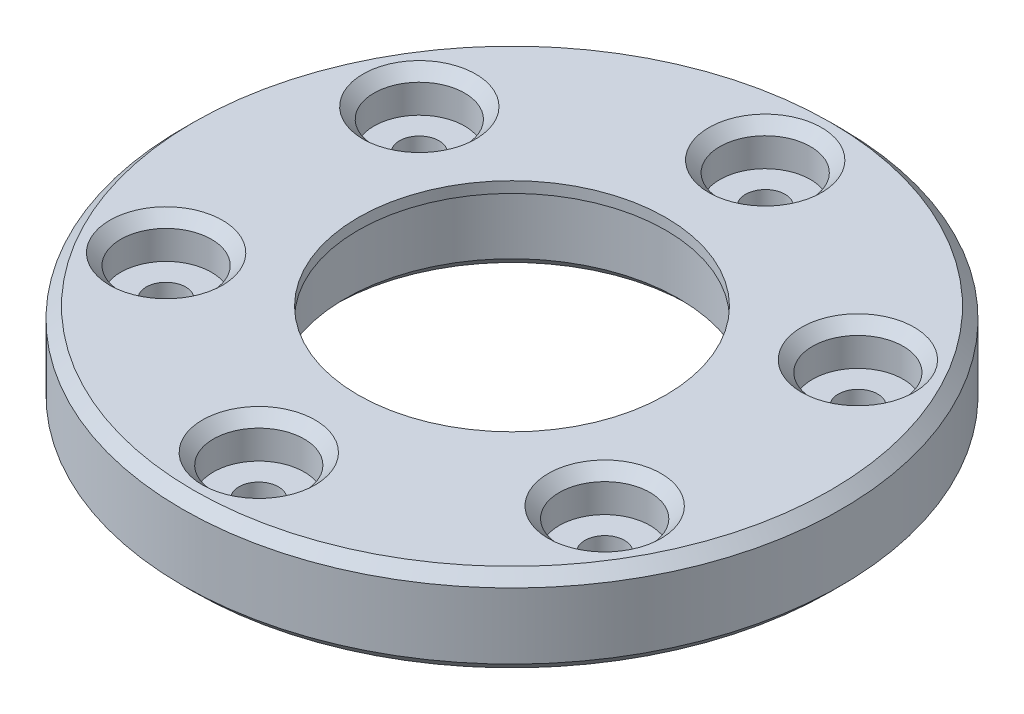
SolidWorks part; units mm, degrees
ref_plane "前视基准面" through (0, 0, 0) normal (0, 0, 1) x (1, 0, 0)
ref_plane "上视基准面" through (0, 0, 0) normal (0, 1, 0) x (1, 0, 0)
ref_plane "右视基准面" through (0, 0, 0) normal (1, 0, 0) x (0, 0, -1)
other "Configuration Table"
sketch "草图1" plane through (0, 0, 0) normal (0, 1, 0) x (1, 0, 0)
  circle A0 centre (0, 0) radius 7
  circle A1 centre (0, 0) radius 15
  circle A2 centre (0, 0) radius 11.525 construction
  circle A3 centre (0, 11.525) radius 2.065
  circle A4 centre (9.9809, 5.7625) radius 2.065
  circle A5 centre (9.9809, -5.7625) radius 2.065
  circle A6 centre (0, -11.525) radius 2.065
  circle A7 centre (-9.9809, -5.7625) radius 2.065
  circle A8 centre (-9.9809, 5.7625) radius 2.065
  point P19 (0, 0)
  dimension "D1" = 14
  dimension "D2" = 30
  dimension "D3" = 23.05
  dimension "D4" = 4.13
  dimension "D5" = 6
extrude "凸台-拉伸1" add sketch "草图1" along normal blind 1.8
sketch "草图2" plane through (0, 0, 0) normal (0, -1, 0) x (-1, 0, 0)
  circle A0 centre (0, 0) radius 7 construction
  circle A1 centre (0, 0) radius 15 construction
  circle A2 centre (0, 0) radius 7
  circle A3 centre (0, 0) radius 15
  circle A4 centre (0, 11.53) radius 0.9
  circle A6 centre (0, 0) radius 11.53 construction
  circle A7 centre (9.9853, 5.765) radius 0.9
  circle A8 centre (9.9853, -5.765) radius 0.9
  circle A9 centre (0, -11.53) radius 0.9
  circle A10 centre (-9.9853, -5.765) radius 0.9
  circle A11 centre (-9.9853, 5.765) radius 0.9
  point P21 (0, 0)
  dimension "D1" = 1.8
  dimension "D2" = 23.06
  dimension "D3" = 6
extrude "凸台-拉伸2" add sketch "草图2" along normal blind 2.2
sketch "草图3" plane through (0, -2.2, 0) normal (0, -1, 0) x (-1, 0, 0)
  circle A0 centre (0, 0) radius 7.6
  dimension "D1" = 15.2
extrude "切除-拉伸1" cut sketch "草图3" against normal blind 3.5
chamfer "倒角1" distance 0.5 angle 45 15 edges at (0, -2.2, -15) (-9.9809, 1.8, -3.6975) (0, 1.8, 13.59) (9.9809, 1.8, -3.6975) (0, 1.8, 15) (0, 1.8, -9.46) (9.9809, 1.8, 7.8275) (-9.9809, 1.8, 7.8275) (9.9853, -2.2, -6.665) (0, -2.2, 10.63) (-9.9853, -2.2, -6.665) (0, -2.2, -12.43) (-9.9853, -2.2, 4.865) (9.9853, -2.2, 4.865) (0, -2.2, -7.6)
chamfer "倒角2" distance 0.3 angle 45 1 edges at (0, 1.3, -7.6)
